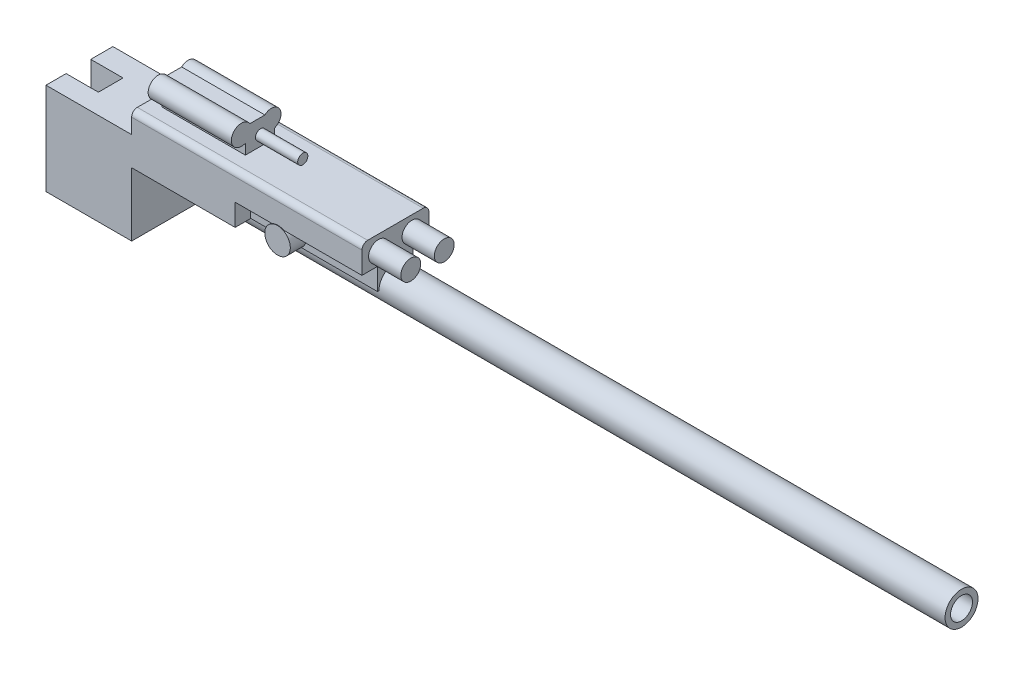
SolidWorks part; units mm, degrees
ref_plane "Front Plane" through (0, 0, 0) normal (0, 0, 1) x (1, 0, 0)
ref_plane "Top Plane" through (0, 0, 0) normal (0, 1, 0) x (1, 0, 0)
ref_plane "Right Plane" through (0, 0, 0) normal (1, 0, 0) x (0, 0, -1)
sketch "Right Side" plane through (0, 0, 0) normal (0, 0, 1) x (1, 0, 0)
  line L0 (-20.9862, -14434.8241) -> (30809.0138, -14434.8241) construction
  dimension "D1" = 30830
sketch "Sketch4" plane through (0, 0, 0) normal (0, 0, 1) x (1, 0, 0)
  line L0 (3015.7408, 3245.2422) -> (3738.627, 3245.2422)
  line L1 (0, 3245.2422) -> (3015.7408, 3245.2422)
  line L2 (0, 3245.2422) -> (0, 0)
  line L3 (0, 0) -> (3015.7408, 0)
  line L4 (3015.7408, 3245.2422) -> (3015.7408, 0)
  line L5 (3738.627, 3899.2821) -> (10864.2194, 3899.2821)
  line L6 (3738.627, 3899.2821) -> (3738.627, 1283.1226)
  line L7 (3738.627, 1283.1226) -> (10864.2194, 1283.1226)
  line L8 (10864.2194, 3899.2821) -> (10864.2194, 1283.1226)
  line L9 (3015.7408, 1433.3167) -> (3738.627, 1433.3167)
extrude "Boss-Extrude1" add sketch "Sketch4" along normal mid plane 2355 contours L4 L1 L2 L3 region at (1507.8704, 1622.6211, 0)
sketch "Sketch5" plane through (0, 0, 0) normal (0, 1, 0) x (1, 0, 0)
  line L0 (421.4888, 34885.5202) -> (31251.4888, 34885.5202) construction
  dimension "D1" = 30830
sketch "Back Side" plane through (0, 0, 0) normal (1, 0, 0) x (0, 0, -1)
  line L0 (-23518.0221, 7218.1179) -> (7311.9779, 7218.1179) construction
  dimension "D1" = 30830
sketch "Sketch7" plane through (3015.7408, 0, 0) normal (1, 0, 0) x (0, 0, -1)
  line L0 (-1177.5, 3977.3698) -> (1177.5, 3977.3698)
  line L1 (1177.5, 3977.3698) -> (1177.5, 2236.8147)
  line L2 (1177.5, 2236.8147) -> (-1177.5, 2236.8147)
  line L3 (-1177.5, 3245.2422) -> (-1177.5, 0) construction
  line L4 (-1177.5, 2236.8147) -> (-1177.5, 3977.3698)
extrude "Boss-Extrude2" add sketch "Sketch7" along normal blind 8106
fillet "Fillet1" radius 200 2 edges at (7068.7408, 3977.3698, -1177.5) (7068.7408, 3977.3698, 1177.5)
sketch "Sketch8" plane through (3015.7408, 0, 0) normal (1, 0, 0) x (0, 0, -1)
  line L0 (-1177.5, 2236.8147) -> (1177.5, 2236.8147) construction
  circle A0 centre (0, 2236.8147) radius 580
  circle A1 centre (0, 2236.8147) radius 386.1554
  dimension "D1" = 1160
extrude "Boss-Extrude3" add sketch "Sketch8" along normal blind 28036
ref_plane "Plane1" through (3445.7408, 0, 0) normal (-1, 0, 0) x (0, 0, 1)
sketch "Sketch10" plane through (3445.7408, 0, 0) normal (-1, 0, 0) x (0, 0, 1)
  line L0 (-977.5, 3977.3698) -> (977.5, 3977.3698) construction
  line L1 (533.501, 4859.3019) -> (-490.686, 4859.3019)
  line L2 (533.501, 4859.3019) -> (533.501, 3977.3698)
  line L3 (533.501, 3977.3698) -> (-490.686, 3977.3698)
  line L4 (-490.686, 4859.3019) -> (-490.686, 3977.3698)
  circle A0 centre (-381.8024, 4610.911) radius 337.9398
  circle A1 centre (673.0082, 4668.7555) radius 353.8883
extrude "Boss-Extrude4" add sketch "Sketch10" against normal blind 2929 contours L2 A1 L1 | A1 L1 A0 L4 L3 L2 | L4 A0 L1 | A0 | A1 region at (3445.7408, 4678.8606, 739.7102) region at (3445.7408, 4322.5491, 79.8112) region at (3445.7408, 4581.7915, -289.5856)
sketch "Sketch11" plane through (6374.7408, 0, 0) normal (1, 0, 0) x (0, 0, -1)
  circle A0 centre (0, 4336.5973) radius 178.5014
extrude "Boss-Extrude5" add sketch "Sketch11" along normal blind 1487
sketch "Sketch12" plane through (11121.7408, 0, 0) normal (1, 0, 0) x (0, 0, -1)
  circle A0 centre (-593.1548, 3459.1291) radius 350
  circle A1 centre (583.8215, 3459.1291) radius 350
  dimension "D1" = 700
  dimension "D2" = 700
extrude "Boss-Extrude6" add sketch "Sketch12" along normal blind 1136
sketch "Sketch13" plane through (0, 0, 0) normal (-1, 0, 0) x (0, 0, 1)
  line L0 (50, 0) -> (-50, 0) construction
  line L1 (-398.76, 3575.6771) -> (469.0428, 3575.6771)
  line L2 (-398.76, 3575.6771) -> (-398.76, 0)
  line L3 (-398.76, 0) -> (469.0428, 0)
  line L4 (469.0428, 3575.6771) -> (469.0428, 0)
extrude "Cut-Extrude1" cut sketch "Sketch13" against normal blind 1136
sketch "Sketch14" plane through (11121.7408, 0, 0) normal (1, 0, 0) x (0, 0, -1)
  line L0 (-1177.5, 3777.3698) -> (-1177.5, 2236.8147) construction
  line L1 (-1177.5, 3007.0922) -> (-627.5889, 3007.0922)
  line L2 (-1177.5, 3007.0922) -> (-1177.5, 2236.8147)
  line L3 (-1177.5, 2236.8147) -> (-627.5889, 2236.8147)
  line L4 (-627.5889, 3007.0922) -> (-627.5889, 2236.8147)
  line L5 (-1177.5, 2236.8147) -> (-580, 2236.8147) construction
  line L6 (0, 3756.293) -> (0, 679.5768) construction
  line L7 (1177.5, 2236.8147) -> (627.5889, 2236.8147)
  line L8 (627.5889, 3007.0922) -> (627.5889, 2236.8147)
  line L9 (1177.5, 3007.0922) -> (627.5889, 3007.0922)
  line L10 (1177.5, 3007.0922) -> (1177.5, 2236.8147)
extrude "Cut-Extrude2" cut sketch "Sketch14" against normal blind 4464
sketch "Sketch16" plane through (0, 0, 627.5889) normal (0, 0, 1) x (1, 0, 0)
  circle A0 centre (8166.722, 2606.0209) radius 450
  dimension "D1" = 900
extrude "Boss-Extrude8" add sketch "Sketch16" along normal blind 566
mirror "Mirror1" about plane through (0, 0, 0) normal (0, 0, 1) of "Boss-Extrude8"
scale "Scale1" scale about origin uniform scaling yes scale factor 0.1
